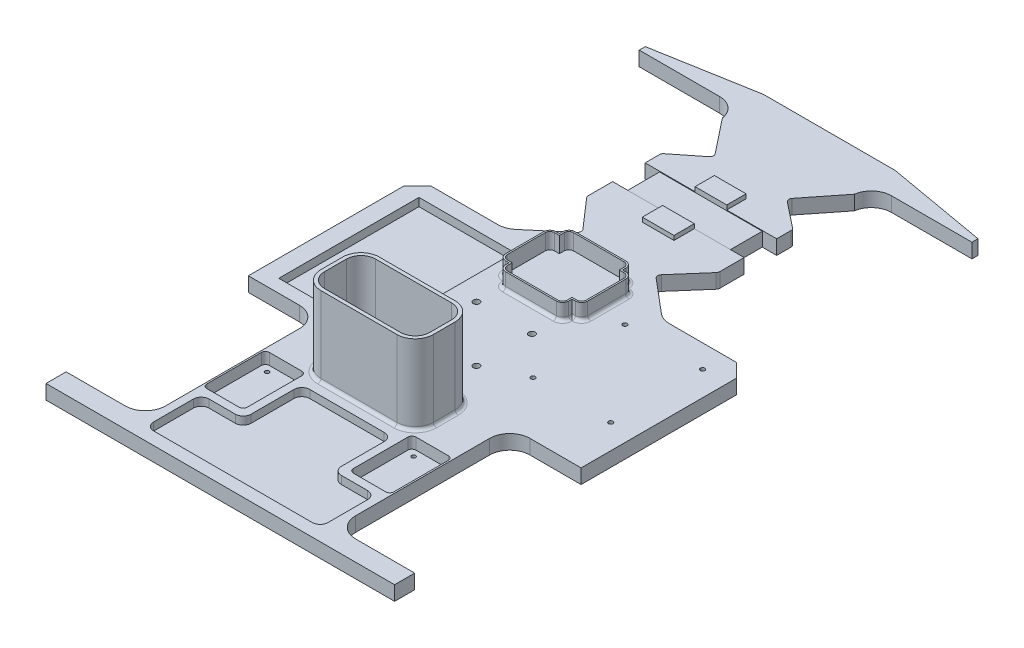
SolidWorks part; units mm, degrees
ref_plane "Front Plane" through (0, 0, 0) normal (0, 0, 1) x (1, 0, 0)
ref_plane "Top Plane" through (0, 0, 0) normal (0, 1, 0) x (1, 0, 0)
ref_plane "Right Plane" through (0, 0, 0) normal (1, 0, 0) x (0, 0, -1)
sketch "Sketch4" plane through (0, 0, 0) normal (0, 1, 0) x (1, 0, 0)
  line L13 (56.7, 201.69) -> (56.7, 186.69)
  line L14 (56.7, 311.69) -> (56.7, 236.69)
  line L15 (139.7, 276.69) -> (139.7, 326.69)
  line L16 (139.7, 236.69) -> (139.7, 276.69)
  line L17 (56.7, 236.69) -> (56.7, 201.69)
  line L20 (139.7, 201.69) -> (139.7, 236.69)
  line L44 (56.7, 326.69) -> (56.7, 311.69)
  line L45 (56.7, 186.69) -> (-6.8, 186.69)
  line L46 (-6.8, 186.69) -> (-6.8, 80.01)
  line L47 (-6.8, 80.01) -> (38.2, 80.01)
  line L48 (38.2, 80.01) -> (38.2, -29.99)
  line L49 (38.2, -29.99) -> (-11.8, -29.99)
  line L50 (-11.8, -29.99) -> (-11.8, -42.69)
  line L51 (-11.8, -42.69) -> (208.2, -42.69)
  line L52 (208.2, -42.69) -> (208.2, -29.99)
  line L53 (208.2, -29.99) -> (158.2, -29.99)
  line L54 (158.2, -29.99) -> (158.2, 80.01)
  line L55 (158.2, 80.01) -> (203.2, 80.01)
  line L56 (203.2, 80.01) -> (203.2, 186.69)
  line L57 (203.2, 186.69) -> (139.7, 186.69)
  line L58 (139.7, 186.69) -> (139.7, 201.69)
  line L59 (139.7, 326.69) -> (203.2, 326.69)
  line L60 (203.2, 326.69) -> (203.2, 330.5)
  line L61 (203.2, 330.5) -> (139.7, 341.6968)
  line L62 (139.7, 341.6968) -> (56.7, 341.6968)
  line L63 (56.7, 341.6968) -> (-6.8, 330.5)
  line L64 (-6.8, 330.5) -> (-6.8, 326.69)
  line L65 (-6.8, 326.69) -> (56.7, 326.69)
  dimension "D2" = 106.68
  dimension "D3" = 110
  dimension "D5" = 140
  dimension "D6" = 63.5
  dimension "D7" = 210
  dimension "D9" = 350
  dimension "D10" = 350
  dimension "D11" = 50
  dimension "D12" = 50
  dimension "D13" = 3.81
  dimension "D14" = 3.81
  dimension "D18" = 63.5
  dimension "D20" = 120
extrude "Boss-Extrude1" add sketch "Sketch4" along normal blind 7.62
sketch "Sketch5" plane through (0, 7.62, 0) normal (0, 1, 0) x (1, 0, 0)
  line L0 (-6.8, 93.4804) -> (6.6704, 80.01)
  line L1 (-6.8, 186.69) -> (-6.8, 80.01) construction
  line L2 (-6.8, 80.01) -> (38.2, 80.01) construction
  line L3 (189.7296, 80.01) -> (203.2, 93.4804)
  line L5 (203.2, 80.01) -> (203.2, 186.69) construction
  line L6 (203.2, 178.2047) -> (194.7147, 186.69)
  line L7 (203.2, 186.69) -> (139.7, 186.69) construction
  line L8 (1.6853, 186.69) -> (-6.8, 178.2047)
  line L9 (56.7, 186.69) -> (-6.8, 186.69) construction
  line L10 (158.2, 80.01) -> (203.2, 80.01) construction
  line L11 (-6.8, 186.69) -> (1.6853, 186.69)
  line L12 (203.2, 186.69) -> (203.2, 178.2047)
  line L13 (203.2, 80.01) -> (189.7296, 80.01)
  line L14 (-6.8, 80.01) -> (-6.8, 93.4804)
  line L15 (-6.8, 178.2047) -> (-6.8, 186.69)
  line L16 (6.6704, 80.01) -> (-6.8, 80.01)
  line L17 (194.7147, 186.69) -> (203.2, 186.69)
  line L18 (203.2, 93.4804) -> (203.2, 80.01)
  line M7 (56.7, 186.69) -> (-6.8, 186.69)
  line M8 (-6.8, 186.69) -> (-6.8, 80.01)
  line M18 (203.2, 80.01) -> (203.2, 186.69)
  line M19 (203.2, 186.69) -> (139.7, 186.69)
  dimension "D1" = 45
  dimension "D2" = 12
  dimension "D3" = 12
  dimension "D4" = 19.05
  dimension "D5" = 19.05
extrude "Cut-Extrude1" cut sketch "Sketch5" against normal through all contours L8 M7 M8 | L6 M18 M19 region at (-3.9716, 7.62, -183.8616) region at (200.3716, 7.62, -183.8616)
fillet "Fillet2" radius 12.7 4 edges at (139.7, 3.81, -186.69) (139.7, 3.81, -326.69) (56.7, 3.81, -186.69) (56.7, 3.81, -326.69)
fillet "Fillet3" radius 12.7 4 edges at (158.2, 3.81, 29.99) (158.2, 3.81, -80.01) (38.2, 3.81, 29.99) (38.2, 3.81, -80.01)
sketch "Sketch9" plane through (0, 7.62, 0) normal (0, 1, 0) x (1, 0, 0)
  line L0 (98.2, -42.69) -> (98.2, 341.6968) construction
  line L1 (-11.8, -42.69) -> (208.2, -42.69) construction
  line L2 (139.7, 341.6968) -> (56.7, 341.6968) construction
  line L3 (56.7, 256.69) -> (139.7, 256.69) construction
  line L6 (56.7, 313.99) -> (56.7, 199.39) construction
  point P11 (56.7, 256.69)
sketch "Sketch6" plane through (0, 7.62, 0) normal (0, 1, 0) x (1, 0, 0)
  line L4 (74.2351, 81.5723) -> (122.1649, 81.5723)
  line L5 (133.6642, 70.073) -> (133.6643, 56.3062)
  line L6 (122.1649, 44.8068) -> (74.2351, 44.8068)
  line L7 (62.7358, 56.3062) -> (62.7357, 70.073)
  line L8 (64.9858, 56.3062) -> (64.9857, 70.073)
  line L9 (122.1649, 47.0568) -> (74.2351, 47.0568)
  line L10 (131.4142, 70.073) -> (131.4143, 56.3062)
  line L11 (74.2351, 79.3223) -> (122.1649, 79.3223)
  line L15 (98.2, -42.69) -> (98.2, 341.6968) construction
  arc A6 (133.6642, 70.073) -> (122.1649, 81.5723) centre (122.1649, 70.073) ccw
  arc A7 (122.1649, 44.8068) -> (133.6643, 56.3062) centre (122.1649, 56.3062) ccw
  arc A8 (62.7358, 56.3062) -> (74.2351, 44.8068) centre (74.2351, 56.3062) ccw
  arc A9 (74.2351, 81.5723) -> (62.7357, 70.073) centre (74.2351, 70.073) ccw
  arc A10 (74.2351, 79.3223) -> (64.9857, 70.073) centre (74.2351, 70.073) ccw
  arc A11 (64.9858, 56.3062) -> (74.2351, 47.0568) centre (74.2351, 56.3062) ccw
  arc A12 (122.1649, 47.0568) -> (131.4143, 56.3062) centre (122.1649, 56.3062) ccw
  arc A13 (131.4142, 70.073) -> (122.1649, 79.3223) centre (122.1649, 70.073) ccw
  point P4 (98.2, 79.3223)
  dimension "D1" = 47.9298
  dimension "D10" = 9.2494
  dimension "D12" = 9.2494
  dimension "D13" = 9.2494
  dimension "D14" = 9.2494
  dimension "D3" = 47.9298
  dimension "D4" = 47.9298
  dimension "D5" = 47.9298
  dimension "D6" = 13.7668
  dimension "D7" = 13.7668
  dimension "D8" = 13.7668
  dimension "D9" = 13.7668
  dimension "D2" = 2.25
extrude "Boss-Extrude2" add sketch "Sketch6" along normal blind 50 contours A9 L7 A8 L6 A7 L5 A6 L4 | A10 L8 A11 L9 A12 L10 A13 L11
fillet "Fillet4" radius 2 8 edges at (66.1038, 7.62, -48.1749) (98.2, 7.62, -44.8068) (130.2962, 7.62, -48.1749) (133.6643, 7.62, -63.1896) (130.2962, 7.62, -78.2043) (98.2, 7.62, -81.5723) (66.1038, 7.62, -78.2043) (62.7358, 7.62, -63.1896)
extrude "Cut-Extrude3" cut sketch "Sketch6<5>" against normal blind 5.08 contours L10 A13 L11 A10 L8 A11 L9 A12 region at (98.2, 7.62, -63.1896)
sketch "Sketch6<5>" plane through (0, 7.62, 0) normal (0, 1, 0) x (1, 0, 0) same geometry as "Sketch6"
sketch "Sketch7" plane through (0, 7.62, 0) normal (0, 1, 0) x (1, 0, 0)
  line L0 (38.2, 25.01) -> (158.2, 25.01) construction
  line L1 (38.2, 67.31) -> (38.2, -17.29) construction
  line L2 (158.2, -17.29) -> (158.2, 67.31) construction
sketch "Sketch8" plane through (0, 7.62, 0) normal (0, 1, 0) x (1, 0, 0)
  line L0 (39.2, 42.22) -> (39.2, 7.8)
  line L1 (38.2, 67.31) -> (38.2, -17.29) construction
  line L2 (41.74, 5.26) -> (62.16, 5.26)
  line L4 (64.7, 7.8) -> (64.7, 42.22)
  line L5 (62.16, 44.76) -> (41.74, 44.76)
  line L6 (38.2, 0) -> (158.2, 0) construction
  line L7 (158.2, -17.29) -> (158.2, 67.31) construction
  line L8 (98.2, 0) -> (98.2, 39.9143)
  line L10 (38.2, 25.01) -> (158.2, 25.01) construction
  line L11 (134.24, 44.76) -> (154.66, 44.76)
  line L12 (131.7, 7.8) -> (131.7, 42.22)
  line L13 (154.66, 5.26) -> (134.24, 5.26)
  line L14 (157.2, 42.22) -> (157.2, 7.8)
  arc A0 (154.66, 44.76) -> (157.2, 42.22) centre (154.66, 42.22) cw
  arc A1 (134.24, 44.76) -> (131.7, 42.22) centre (134.24, 42.22) ccw
  arc A2 (131.7, 7.8) -> (134.24, 5.26) centre (134.24, 7.8) ccw
  arc A3 (154.66, 5.26) -> (157.2, 7.8) centre (154.66, 7.8) ccw
  arc A4 (41.74, 5.26) -> (39.2, 7.8) centre (41.74, 7.8) cw
  arc A5 (64.7, 7.8) -> (62.16, 5.26) centre (62.16, 7.8) cw
  arc A6 (62.16, 44.76) -> (64.7, 42.22) centre (62.16, 42.22) cw
  arc A7 (41.74, 44.76) -> (39.2, 42.22) centre (41.74, 42.22) ccw
  point P7 (39.3366, 7.8963)
  point P11 (64.7, 5.26)
  point P12 (64.7, 25.01)
  point P19 (38.2, 44.76)
  point P39 (158.2, 44.76)
  point P40 (131.7, 5.26)
  point P41 (157.0634, 7.8963)
  dimension "D3" = 2.54
  dimension "D1" = 25.5
  dimension "D2" = 39.5
  dimension "D4" = 20.42
  dimension "D5" = 1
extrude "Cut-Extrude4" cut sketch "Sketch8" against normal blind 7.15 contours L5 A7 A4 L2 A5 L4 A6 | L13 A3 A0 L11 A1 L12 A2 region at (51.95, 7.62, -25.01) region at (144.45, 7.62, -25.01)
ref_plane "Plane2" through (61.1942, 2.54, -173.9987) normal (-1, 0, 0) x (0, 0, 1)
sketch "Sketch11" plane through (0, 7.62, 0) normal (0, 1, 0) x (1, 0, 0)
  line L0 (44, 186.69) -> (1.6853, 186.69) construction
  line L1 (-6.8, 178.2047) -> (-6.8, 80.01) construction
  line L12 (4.2, 88.23) -> (64.45, 88.23)
  line L13 (64.45, 88.23) -> (64.45, 176.69)
  line L14 (64.45, 176.69) -> (4.2, 176.69)
  line L15 (4.2, 176.69) -> (4.2, 88.23)
  dimension "D1" = 60.25
  dimension "D2" = 88.46
  dimension "D3" = 10
  dimension "D4" = 11
sketch "Sketch12" plane through (0, 7.62, 0) normal (0, 1, 0) x (1, 0, 0)
  line L0 (66.7, 254.508) -> (139.7, 254.508) construction
  line L3 (44, 186.69) -> (1.6853, 186.69) construction
  dimension "D1" = 67.818
sketch "Sketch13" plane through (0, 7.62, 0) normal (0, 1, 0) x (1, 0, 0)
  line L0 (56.7, 313.99) -> (56.7, 199.39) construction
  line L1 (56.7, 266.94) -> (139.7, 266.94)
  line L2 (56.7, 266.94) -> (56.7, 246.44)
  line L3 (56.7, 246.44) -> (139.7, 246.44)
  line L4 (139.7, 266.94) -> (139.7, 246.44)
  line L5 (139.7, 199.39) -> (139.7, 313.99) construction
  line L6 (56.7, 313.99) -> (56.7, 199.39) construction
  point P12 (56.7, 256.69)
  point P13 (56.7, 256.69)
  dimension "D1" = 20.5
extrude "Cut-Extrude5" cut sketch "Sketch13" against normal blind 0.435 contours L2 L1 L4 L3
sketch "Sketch14" plane through (56.7, 0, 0) normal (-1, 0, 0) x (0, 0, 1)
  line L0 (-313.99, 0) -> (-199.39, 0) construction
  line L1 (-266.94, 7.185) -> (-246.44, 7.185)
  line L2 (-266.94, 7.185) -> (-266.94, 0)
  line L3 (-266.94, 0) -> (-246.44, 0)
  line L4 (-246.44, 7.185) -> (-246.44, 0)
  line L5 (-246.44, 7.185) -> (-246.44, 7.62) construction
extrude "Cut-Extrude6" cut sketch "Sketch14" against normal blind 9.1
sketch "Sketch15" plane through (139.7, 0, 0) normal (1, 0, 0) x (0, 0, -1)
  line L1 (246.44, 7.185) -> (266.94, 7.185)
  line L2 (246.44, 7.185) -> (246.44, 0)
  line L3 (246.44, 0) -> (266.94, 0)
  line L4 (266.94, 7.185) -> (266.94, 0)
extrude "Cut-Extrude7" cut sketch "Sketch15" against normal blind 9.1
extrude "Cut-Extrude8" cut sketch "Sketch11" against normal blind 5.08
sketch "Sketch16" plane through (0, 0, 0) normal (0, -1, 0) x (1, 0, 0)
  line L32 (130.6, -246.44) -> (139.7, -246.44)
  line L33 (139.7, -246.44) -> (139.7, -199.39)
  line L34 (152.4, -186.69) -> (194.7147, -186.69)
  line L35 (194.7147, -186.69) -> (203.2, -178.2047)
  line L36 (203.2, -178.2047) -> (203.2, -80.01)
  line L37 (203.2, -80.01) -> (170.9, -80.01)
  line L38 (158.2, -67.31) -> (158.2, 17.29)
  line L39 (170.9, 29.99) -> (208.2, 29.99)
  line L40 (208.2, 29.99) -> (208.2, 42.69)
  line L41 (208.2, 42.69) -> (-11.8, 42.69)
  line L42 (-11.8, 42.69) -> (-11.8, 29.99)
  line L43 (-11.8, 29.99) -> (25.5, 29.99)
  line L44 (38.2, 17.29) -> (38.2, -67.31)
  line L45 (25.5, -80.01) -> (-6.8, -80.01)
  line L46 (-6.8, -80.01) -> (-6.8, -178.2047)
  line L47 (-6.8, -178.2047) -> (1.6853, -186.69)
  line L48 (1.6853, -186.69) -> (44, -186.69)
  line L49 (56.7, -199.39) -> (56.7, -246.44)
  line L50 (56.7, -246.44) -> (65.8, -246.44)
  line L51 (65.8, -246.44) -> (65.8, -266.94)
  line L52 (65.8, -266.94) -> (56.7, -266.94)
  line L53 (56.7, -266.94) -> (56.7, -313.99)
  line L54 (44, -326.69) -> (-6.8, -326.69)
  line L55 (-6.8, -326.69) -> (-6.8, -330.5)
  line L56 (-6.8, -330.5) -> (56.7, -341.6968)
  line L57 (56.7, -341.6968) -> (139.7, -341.6968)
  line L58 (139.7, -341.6968) -> (203.2, -330.5)
  line L59 (203.2, -330.5) -> (203.2, -326.69)
  line L60 (203.2, -326.69) -> (152.4, -326.69)
  line L62 (139.7, -266.94) -> (130.6, -266.94)
  line L63 (130.6, -266.94) -> (130.6, -246.44)
  line L64 (130.6, -246.44) -> (139.7, -246.44)
  line L65 (139.7, -246.44) -> (139.7, -199.39)
  line L66 (152.4, -186.69) -> (194.7147, -186.69)
  line L67 (194.7147, -186.69) -> (203.2, -178.2047)
  line L68 (203.2, -178.2047) -> (203.2, -80.01)
  line L69 (203.2, -80.01) -> (170.9, -80.01)
  line L70 (158.2, -67.31) -> (158.2, 17.29)
  line L71 (170.9, 29.99) -> (208.2, 29.99)
  line L72 (208.2, 29.99) -> (208.2, 42.69)
  line L73 (208.2, 42.69) -> (-11.8, 42.69)
  line L74 (-11.8, 42.69) -> (-11.8, 29.99)
  line L75 (-11.8, 29.99) -> (25.5, 29.99)
  line L76 (38.2, 17.29) -> (38.2, -67.31)
  line L77 (25.5, -80.01) -> (-6.8, -80.01)
  line L78 (-6.8, -80.01) -> (-6.8, -178.2047)
  line L79 (-6.8, -178.2047) -> (1.6853, -186.69)
  line L80 (1.6853, -186.69) -> (44, -186.69)
  line L81 (56.7, -199.39) -> (56.7, -246.44)
  line L82 (56.7, -246.44) -> (65.8, -246.44)
  line L83 (65.8, -246.44) -> (65.8, -266.94)
  line L84 (65.8, -266.94) -> (56.7, -266.94)
  line L86 (44, -326.69) -> (-6.8, -326.69)
  line L87 (-6.8, -326.69) -> (-6.8, -330.5)
  line L88 (-6.8, -330.5) -> (56.7, -341.6968)
  line L89 (56.7, -341.6968) -> (139.7, -341.6968)
  line L90 (139.7, -341.6968) -> (203.2, -330.5)
  line L91 (203.2, -330.5) -> (203.2, -326.69)
  line L92 (203.2, -326.69) -> (152.4, -326.69)
  line L94 (139.7, -266.94) -> (130.6, -266.94)
  line L95 (130.6, -266.94) -> (130.6, -246.44)
  line L96 (56.7, -266.94) -> (56.7, -313.99)
  line L97 (139.7, -313.99) -> (139.7, -266.94)
  line L98 (139.7, -313.99) -> (139.7, -266.94)
  arc A8 (152.4, -186.69) -> (139.7, -199.39) centre (152.4, -199.39) ccw
  arc A9 (158.2, -67.31) -> (170.9, -80.01) centre (170.9, -67.31) ccw
  arc A10 (170.9, 29.99) -> (158.2, 17.29) centre (170.9, 17.29) ccw
  arc A11 (38.2, 17.29) -> (25.5, 29.99) centre (25.5, 17.29) ccw
  arc A12 (25.5, -80.01) -> (38.2, -67.31) centre (25.5, -67.31) ccw
  arc A13 (56.7, -199.39) -> (44, -186.69) centre (44, -199.39) ccw
  arc A14 (44, -326.69) -> (56.7, -313.99) centre (44, -313.99) ccw
  arc A16 (152.4, -186.69) -> (139.7, -199.39) centre (152.4, -199.39) ccw
  arc A17 (158.2, -67.31) -> (170.9, -80.01) centre (170.9, -67.31) ccw
  arc A18 (170.9, 29.99) -> (158.2, 17.29) centre (170.9, 17.29) ccw
  arc A19 (38.2, 17.29) -> (25.5, 29.99) centre (25.5, 17.29) ccw
  arc A20 (25.5, -80.01) -> (38.2, -67.31) centre (25.5, -67.31) ccw
  arc A22 (44, -326.69) -> (56.7, -313.99) centre (44, -313.99) ccw
  arc A24 (56.7, -199.39) -> (44, -186.69) centre (44, -199.39) ccw
  arc A26 (139.7, -313.99) -> (152.4, -326.69) centre (152.4, -313.99) ccw
  arc A27 (139.7, -313.99) -> (152.4, -326.69) centre (152.4, -313.99) ccw
  dimension "D1" = 0
extrude "Boss-Extrude3" add sketch "Sketch16" along normal blind 1.5
sketch "Sketch17" plane through (0, 7.62, 0) normal (0, 1, 0) x (1, 0, 0)
  line L1 (88.2, 279.1287) -> (108.2, 279.1287)
  line L2 (88.2, 279.1287) -> (88.2, 266.94)
  line L3 (88.2, 266.94) -> (108.2, 266.94)
  line L4 (108.2, 279.1287) -> (108.2, 266.94)
  line L5 (108.4582, 279.1287) -> (88.4582, 279.1287) construction
  line L7 (56.7, 266.94) -> (139.7, 266.94) construction
  line L9 (88.2, 246.44) -> (108.2, 246.44)
  line L10 (88.2, 246.44) -> (88.2, 233.6287)
  line L11 (88.2, 233.6287) -> (108.2, 233.6287)
  line L12 (108.2, 246.44) -> (108.2, 233.6287)
  line L13 (108.4582, 233.6287) -> (88.4582, 233.6287) construction
  dimension "D2" = 20
  dimension "D3" = 20
extrude "Boss-Extrude4" add sketch "Sketch17" along normal blind 2.74 contours L12 L9 L10 L11 | L2 L3 L4 L1 region at (98.2, 7.62, -240.0344)
sketch "Sketch18" plane through (0, 7.62, 0) normal (0, 1, 0) x (1, 0, 0)
  circle A0 centre (79.4214, 137.7487) radius 2
  circle A1 centre (79.4214, 102.7487) radius 2
  circle A2 centre (114.4214, 137.7487) radius 2
  circle A3 centre (114.4214, 102.7487) radius 2
  circle A4 centre (138.7, 114.19) radius 1.375
  circle A5 centre (187.7, 114.19) radius 1.375
  circle A6 centre (187.7, 172.19) radius 1.375
  circle A7 centre (138.7, 172.19) radius 1.375
  circle A8 centre (59.364, 40.4974) radius 1.27
  circle A9 centre (44.524, 40.4974) radius 1.27
  circle A10 centre (44.524, 9.5274) radius 1.27
  circle A11 centre (59.364, 9.5274) radius 1.27
  circle A12 centre (137.024, 9.5274) radius 1.27
  circle A13 centre (151.864, 9.5274) radius 1.27
  circle A14 centre (151.864, 40.4974) radius 1.27
  circle A15 centre (137.024, 40.4974) radius 1.27
  circle A16 centre (98.4582, 238.8787) radius 1
  circle A17 centre (98.4582, 273.8787) radius 1
  point P54 (0, 0)
  point P55 (0, 0)
  point P56 (0, 0)
  point P57 (0, 0)
  point P58 (0, 0)
  point P59 (0, 0)
  point P60 (0, 0)
  point P61 (0, 0)
extrude "Cut-Extrude9" cut sketch "Sketch18" against normal through all
sketch "Sketch20" plane through (0, 7.62, 0) normal (0, 1, 0) x (1, 0, 0)
  line L2 (121.2942, 208.9819) -> (139.7, 230.1083)
  line L3 (139.7, 199.39) -> (139.7, 246.44) construction
  line L4 (56.7, 272.4372) -> (139.7, 272.4372) construction
  line L5 (139.8335, 315.8264) -> (139.7, 313.99)
  line L6 (56.7, 313.99) -> (56.7, 266.94) construction
  line L7 (139.7, 266.94) -> (139.7, 313.99) construction
  line L8 (139.7, 272.4372) -> (98.2, 272.4372) construction
  line L9 (98.2, 272.4372) -> (98.2, 206.3643) construction
  line L13 (56.7, 277.1677) -> (75.4287, 291.985)
  line L14 (75.4287, 291.985) -> (56.5665, 315.8264)
  line L15 (56.5665, 315.8264) -> (56.7, 313.99)
  line L17 (120.9713, 291.985) -> (139.8335, 315.8264)
  line L18 (139.7, 277.1677) -> (120.9713, 291.985)
  line L20 (56.7, 313.99) -> (56.7, 277.1677)
  line L21 (139.7, 277.1677) -> (139.7, 313.99)
  line L22 (139.7, 199.39) -> (139.7, 230.1083)
  line L25 (144.2193, 189.6758) -> (121.2942, 208.9819)
  line L28 (75.1058, 208.9819) -> (56.7, 230.1083)
  line L29 (56.7, 199.39) -> (56.7, 230.1083)
  line L30 (52.1807, 189.6758) -> (75.1058, 208.9819)
  arc A0 (56.7, 313.99) -> (44, 326.69) centre (44, 313.99) ccw construction
  arc A1 (139.7, 199.39) -> (152.4, 186.69) centre (152.4, 199.39) ccw construction
  arc A2 (44, 186.69) -> (56.7, 199.39) centre (44, 199.39) ccw construction
  arc A3 (139.7, 199.39) -> (144.2193, 189.6758) centre (152.4, 199.39) ccw
  arc A7 (56.7, 199.39) -> (52.1807, 189.6758) centre (44, 199.39) cw
extrude "Cut-Extrude10" cut sketch "Sketch20" against normal through all
sketch "Sketch21" plane through (0, 7.62, 0) normal (0, 1, 0) x (1, 0, 0)
  line L0 (38.2, 67.31) -> (38.2, -17.29) construction
  line L1 (74.7, 37.2676) -> (121.7, 37.2676)
  line L2 (69.7, 32.2676) -> (69.7, 5.26)
  line L3 (69.7, -34.69) -> (126.7, -34.69)
  line L4 (126.7, 32.2676) -> (126.7, 5.26)
  line L5 (131.7, 0.26) -> (148.2, 0.26)
  line L7 (126.7, -34.69) -> (148.2, -34.69)
  line L8 (153.2, -4.74) -> (153.2, -29.69)
  line L9 (64.7, 0.26) -> (48.2, 0.26)
  line L11 (69.7, -34.69) -> (48.2, -34.69)
  line L12 (43.2, -4.74) -> (43.2, -29.69)
  line L13 (158.2, -17.29) -> (158.2, 67.31) construction
  line L14 (-11.8, -42.69) -> (208.2, -42.69) construction
  line L15 (64.7, 7.8) -> (64.7, 42.22) construction
  line L16 (131.7, 7.8) -> (131.7, 42.22) construction
  line L17 (41.74, 5.26) -> (62.16, 5.26) construction
  line L18 (154.66, 5.26) -> (134.24, 5.26) construction
  arc A0 (121.7, 37.2676) -> (126.7, 32.2676) centre (121.7, 32.2676) cw
  arc A1 (74.7, 37.2676) -> (69.7, 32.2676) centre (74.7, 32.2676) ccw
  arc A2 (48.2, -34.69) -> (43.2, -29.69) centre (48.2, -29.69) cw
  arc A3 (148.2, -34.69) -> (153.2, -29.69) centre (148.2, -29.69) ccw
  arc A4 (148.2, 0.26) -> (153.2, -4.74) centre (148.2, -4.74) cw
  arc A5 (48.2, 0.26) -> (43.2, -4.74) centre (48.2, -4.74) ccw
  arc A6 (131.7, 0.26) -> (126.7, 5.26) centre (131.7, 5.26) cw
  arc A7 (64.7, 0.26) -> (69.7, 5.26) centre (64.7, 5.26) ccw
  dimension "D8" = 5
  dimension "D1" = 5
  dimension "D2" = 5
  dimension "D3" = 8
  dimension "D4" = 5
  dimension "D5" = 5
  dimension "D6" = 5
  dimension "D7" = 5
extrude "Cut-Extrude11" cut sketch "Sketch21" against normal blind 5
fillet "Fillet5" radius 2.5 8 edges at (139.7, 3.06, -230.1083) (139.7, 3.06, -277.1677) (120.9713, 3.06, -291.985) (56.7, 3.06, -277.1677) (75.4287, 3.06, -291.985) (121.2942, 3.06, -208.9819) (56.7, 3.06, -230.1083) (75.1058, 3.06, -208.9819)
sketch "Sketch22" plane through (0, 7.62, 0) normal (0, 1, 0) x (1, 0, 0)
  line L12 (79.3, 160.403) -> (76.2, 160.403)
  line L13 (73.3, 163.303) -> (73.3, 187.303)
  line L14 (76.2, 190.203) -> (79.3, 190.203)
  line L15 (79.3, 190.203) -> (79.3, 193.303)
  line L16 (82.2, 196.203) -> (114.2, 196.203)
  line L17 (117.1, 193.303) -> (117.1, 190.203)
  line L18 (117.1, 190.203) -> (120.2, 190.203)
  line L19 (123.1, 187.303) -> (123.1, 163.303)
  line L30 (120.2, 160.403) -> (117.1, 160.403)
  line L31 (117.1, 160.403) -> (117.1, 157.303)
  line L32 (114.2, 154.403) -> (82.2, 154.403)
  line L33 (79.3, 157.303) -> (79.3, 160.403)
  line L34 (78.3, 159.403) -> (76.2, 159.403)
  line L35 (72.3, 163.303) -> (72.3, 187.303)
  line L36 (76.2, 191.203) -> (78.3, 191.203)
  line L37 (78.3, 191.203) -> (78.3, 193.303)
  line L38 (82.2, 197.203) -> (114.2, 197.203)
  line L39 (118.1, 193.303) -> (118.1, 191.203)
  line L40 (118.1, 191.203) -> (120.2, 191.203)
  line L41 (124.1, 187.303) -> (124.1, 163.303)
  line L42 (120.2, 159.403) -> (118.1, 159.403)
  line L43 (118.1, 159.403) -> (118.1, 157.303)
  line L44 (114.2, 153.403) -> (82.2, 153.403)
  line L45 (78.3, 157.303) -> (78.3, 159.403)
  arc A8 (73.3, 163.303) -> (76.2, 160.403) centre (76.2, 163.303) ccw
  arc A9 (76.2, 190.203) -> (73.3, 187.303) centre (76.2, 187.303) ccw
  arc A10 (82.2, 196.203) -> (79.3, 193.303) centre (82.2, 193.303) ccw
  arc A11 (117.1, 193.303) -> (114.2, 196.203) centre (114.2, 193.303) ccw
  arc A12 (123.1, 187.303) -> (120.2, 190.203) centre (120.2, 187.303) ccw
  arc A13 (120.2, 160.403) -> (123.1, 163.303) centre (120.2, 163.303) ccw
  arc A14 (114.2, 154.403) -> (117.1, 157.303) centre (114.2, 157.303) ccw
  arc A15 (79.3, 157.303) -> (82.2, 154.403) centre (82.2, 157.303) ccw
  arc A24 (72.3, 163.303) -> (76.2, 159.403) centre (76.2, 163.303) ccw
  arc A25 (76.2, 191.203) -> (72.3, 187.303) centre (76.2, 187.303) ccw
  arc A26 (82.2, 197.203) -> (78.3, 193.303) centre (82.2, 193.303) ccw
  arc A27 (118.1, 193.303) -> (114.2, 197.203) centre (114.2, 193.303) ccw
  arc A28 (124.1, 187.303) -> (120.2, 191.203) centre (120.2, 187.303) ccw
  arc A29 (120.2, 159.403) -> (124.1, 163.303) centre (120.2, 163.303) ccw
  arc A30 (114.2, 153.403) -> (118.1, 157.303) centre (114.2, 157.303) ccw
  arc A31 (78.3, 157.303) -> (82.2, 153.403) centre (82.2, 157.303) ccw
  dimension "D1" = 1
extrude "Boss-Extrude5" add sketch "Sketch22" along normal blind 10
fillet "Fillet6" radius 2 20 edges at (119.15, 7.62, -159.403) (122.9577, 7.62, -160.5453) (119.15, 7.62, -191.203) (122.9577, 7.62, -190.0607) (118.1, 7.62, -192.253) (116.9577, 7.62, -196.0607) (78.3, 7.62, -192.253) (79.4423, 7.62, -196.0607) (78.3, 7.62, -158.353) (118.1, 7.62, -158.353) (116.9577, 7.62, -154.5453) (98.2, 7.62, -153.403) (77.25, 7.62, -191.203) (73.4423, 7.62, -190.0607) (77.25, 7.62, -159.403) (73.4423, 7.62, -160.5453) (124.1, 7.62, -175.303) (98.2, 7.62, -197.203) (79.4423, 7.62, -154.5453) (72.3, 7.62, -175.303)
